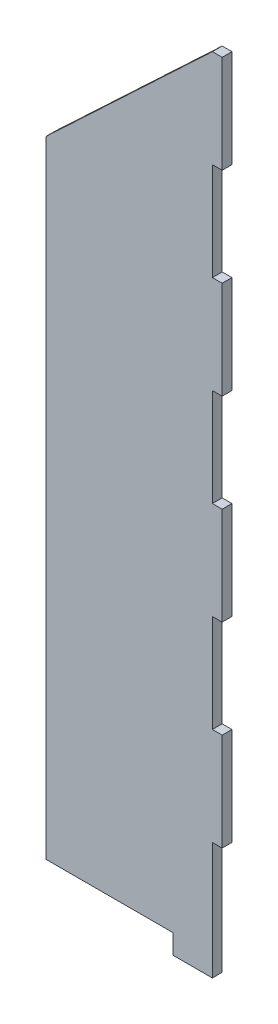
SolidWorks part; units mm, degrees
ref_plane "Front Plane" through (0, 0, 0) normal (0, 0, 1) x (1, 0, 0)
ref_plane "Top Plane" through (0, 0, 0) normal (0, 1, 0) x (1, 0, 0)
ref_plane "Right Plane" through (0, 0, 0) normal (1, 0, 0) x (0, 0, -1)
sketch "Sketch1" plane through (0, 0, 0) normal (0, 0, 1) x (1, 0, 0)
  line L0 (-26.9875, -101.6) -> (-26.9875, 101.6)
  line L1 (-26.9875, 101.6) -> (26.9875, 152.4)
  line L2 (26.9875, 152.4) -> (26.9875, -101.6)
  line L3 (26.9875, -101.6) -> (-26.9875, -101.6)
  line L4 (-26.9875, 0) -> (26.9875, 0) construction
  line L5 (26.9875, 120.65) -> (26.9875, 88.9)
  line L6 (26.9875, 152.4) -> (30.1625, 152.4)
  line L7 (26.9875, 152.4) -> (26.9875, 120.65)
  line L8 (26.9875, 120.65) -> (30.1625, 120.65)
  line L9 (30.1625, 152.4) -> (30.1625, 120.65)
  line L10 (26.9875, 120.65) -> (30.1625, 120.65)
  line L11 (30.1625, 120.65) -> (30.1625, 88.9)
  line L12 (26.9875, 88.9) -> (30.1625, 88.9)
  line L13 (26.9875, 88.9) -> (26.9875, 57.15)
  line L14 (26.9875, 88.9) -> (30.1625, 88.9)
  line L15 (30.1625, 88.9) -> (30.1625, 57.15)
  line L16 (26.9875, 57.15) -> (30.1625, 57.15)
  line L17 (26.9875, 57.15) -> (26.9875, 25.4)
  line L18 (26.9875, 57.15) -> (30.1625, 57.15)
  line L19 (30.1625, 57.15) -> (30.1625, 25.4)
  line L20 (26.9875, 25.4) -> (30.1625, 25.4)
  line L21 (26.9875, 25.4) -> (26.9875, -6.35)
  line L22 (26.9875, 25.4) -> (30.1625, 25.4)
  line L23 (30.1625, 25.4) -> (30.1625, -6.35)
  line L24 (26.9875, -6.35) -> (30.1625, -6.35)
  line L25 (26.9875, -6.35) -> (26.9875, -38.1)
  line L26 (26.9875, -6.35) -> (30.1625, -6.35)
  line L27 (30.1625, -6.35) -> (30.1625, -38.1)
  line L28 (26.9875, -38.1) -> (30.1625, -38.1)
  line L29 (26.9875, -38.1) -> (26.9875, -69.85)
  line L30 (26.9875, -38.1) -> (30.1625, -38.1)
  line L31 (30.1625, -38.1) -> (30.1625, -69.85)
  line L32 (26.9875, -69.85) -> (30.1625, -69.85)
  line L33 (26.9875, -69.85) -> (26.9875, -101.6)
  line L42 (26.9875, -69.85) -> (30.1625, -69.85)
  line L43 (30.1625, -69.85) -> (30.1625, -101.6)
  line L44 (26.9875, -101.6) -> (30.1625, -101.6)
  line L46 (14.2875, -101.6) -> (26.9875, -101.6)
  line L47 (14.2875, -101.6) -> (14.2875, -107.95)
  line L48 (14.2875, -107.95) -> (26.9875, -107.95)
  line L49 (26.9875, -101.6) -> (26.9875, -107.95)
  point P2 (0, 0)
  dimension "D1" = 53.975
  dimension "D2" = 254
  dimension "D3" = 203.2
  dimension "D4" = 3.175
  dimension "D6" = 31.75
  dimension "D7" = 12.7
  dimension "D8" = 6.35
  dimension "D5" = 8
extrude "Boss-Extrude1" add sketch "Sketch1" along normal blind 3.175 contours L4 L0 L3 L2 L21 | L0 L4 L2 L1 | L9 L6 L2 L8 | L2 L16 L15 L12 | L2 L21 L24 L23 L20 | L2 L32 L31 L28 | L32 L3 L47 region at (0, -50.8, 0) region at (1.7992, 64.3467, 0) region at (20.6375, -104.775, 0) region at (28.575, 9.525, 0) region at (28.575, 136.525, 0) region at (28.575, -53.975, 0) region at (28.575, 73.025, 0)
equation "\"Height\"= 12in"
equation "\"Depth\"= 7in"
equation "\"WallThickness\"= 0.125in"
equation "\"FloorThickness\"= 0.25in"
equation "\"D1@Sketch1\"=(\"Depth\"-2.75)/2"
equation "\"D4@Sketch1\"=\"WallThickness\""
equation "\"D6@Sketch1\"=\"D2@Sketch1\"/\"D5@Sketch1\""
equation "\"D8@Sketch1\"=\"FloorThickness\""
equation "\"D1@Boss-Extrude1\"=\"WallThickness\""
equation "\"Width\" = 30in"
